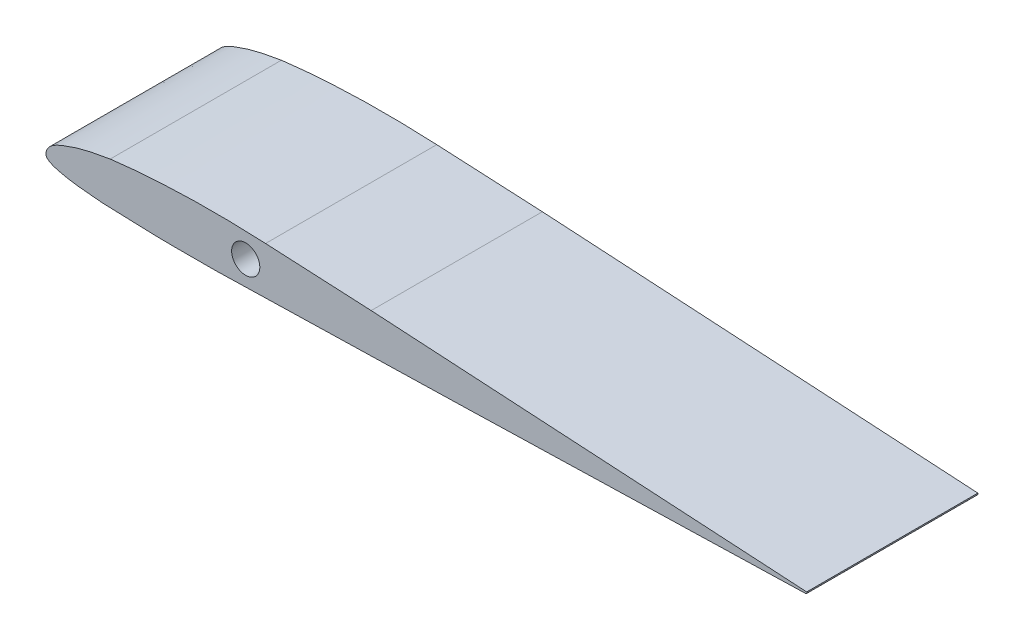
SolidWorks part; units mm, degrees
ref_plane "Front Plane" through (0, 0, 0) normal (0, 0, 1) x (1, 0, 0)
ref_plane "Top Plane" through (0, 0, 0) normal (0, 1, 0) x (1, 0, 0)
ref_plane "Right Plane" through (0, 0, 0) normal (1, 0, 0) x (0, 0, -1)
sketch "Sketch3" plane through (0, 0, 0) normal (0, 0, 1) x (1, 0, 0)
  line L0 (202.9941, 8.6587) -> (110.5837, 6.1553)
  line L1 (110.5837, 6.1553) -> (45.2437, 4.5477)
  line L2 (58.6413, 17.491) -> (86.8465, 16.0766)
  line L3 (0, 35.3471) -> (0, -15.2378) construction
  line L4 (86.8465, 16.0766) -> (160.9786, 11.667)
  line L5 (160.9786, 11.667) -> (203.1607, 9.1578)
  line L6 (203.1999, 14.8061) -> (203.1999, -9.9364) construction
  line L7 (0, 0) -> (203.1999, 0) construction
  line L8 (50.8, 72.9775) -> (50.8, -63.9956) construction
  arc A0 (203.1607, 9.1578) -> (202.9941, 8.6587) centre (202.8278, 8.9915) cw
  spline S0 degree 3 poles (45.2437, 4.5477) (38.9236, 4.5689) (32.5987, 4.4374) (26.2837, 4.6938) (22.3484, 4.8536) (18.4102, 4.9373) (14.4749, 5.0971) (14.4129, 5.0996) (14.3701, 5.1734) (14.3085, 5.1801) (13.7572, 5.24) (0.0923, 5.9331) (0.0016, 8.7406) (-0.0833, 11.3694) (3.2406, 12.5979) (5.1525, 13.3198) (6.7026, 13.905) (8.2818, 14.4263) (9.8909, 14.8216) (12.2626, 15.4044) (14.6912, 15.8835) (17.1496, 16.275) knots 0 0 0 0 1 1 1 2 2 2 3 3 3 4 4 4 5 5 5 6 6 6 6.272168 6.272168 6.272168 6.272168
  spline S1 degree 3 poles (17.1496, 16.275) (28.8325, 17.7257) (42.6703, 18.2919) (58.6413, 17.491) knots 0 0 0 0 1 1 1 1
  point P17 (50.8, 17.7806)
  point P18 (50.8, 4.6844)
  dimension "D1" = 203.1999
  dimension "D2" = 50.8
extrude "Airfoil" add sketch "Sketch3" along normal blind 45.72
sketch "Sketch8" plane through (0, 0, 0) normal (0, 0, -1) x (-1, 0, 0)
  line L0 (0, 16.6795) -> (0, -1.637) construction
  line L1 (-203.1999, 12.5809) -> (-203.1999, 6.3994) construction
  line L2 (-53.34, 11.2284) -> (-53.34, 17.7099) construction
  line L3 (-53.34, 11.2284) -> (-53.34, 4.7469) construction
  line L4 (-45.2437, 4.5477) -> (-110.5837, 6.1553) construction
  circle A0 centre (-53.34, 11.2284) radius 3.7592
  arc A1 (-203.1607, 9.1578) -> (-202.9941, 8.6587) centre (-202.8278, 8.9915) ccw construction
  spline S0 degree 3 poles (-17.1496, 16.275) (-14.6912, 15.8835) (-12.2626, 15.4044) (-9.8909, 14.8216) (-8.2818, 14.4263) (-6.7026, 13.905) (-5.1525, 13.3198) (-3.2406, 12.5979) (0.0833, 11.3694) (-0.0016, 8.7406) (-0.0923, 5.9331) (-13.7572, 5.24) (-14.3085, 5.1801) (-14.3701, 5.1734) (-14.4129, 5.0996) (-14.4749, 5.0971) (-18.4102, 4.9373) (-22.3484, 4.8536) (-26.2837, 4.6938) (-32.5987, 4.4374) (-38.9236, 4.5689) (-45.2437, 4.5477) knots 0 0 0 0 0.272168 0.272168 0.272168 1.272168 1.272168 1.272168 2.272168 2.272168 2.272168 3.272168 3.272168 3.272168 4.272168 4.272168 4.272168 5.272168 5.272168 5.272168 6.272168 6.272168 6.272168 6.272168 construction
  spline S1 degree 3 poles (-58.6413, 17.491) (-42.6703, 18.2919) (-28.8325, 17.7257) (-17.1496, 16.275) knots 0 0 0 0 1 1 1 1 construction
  dimension "D1" = 7.5184
  dimension "D2" = 53.34
extrude "Camera Channel" cut sketch "Sketch8" against normal up to next
